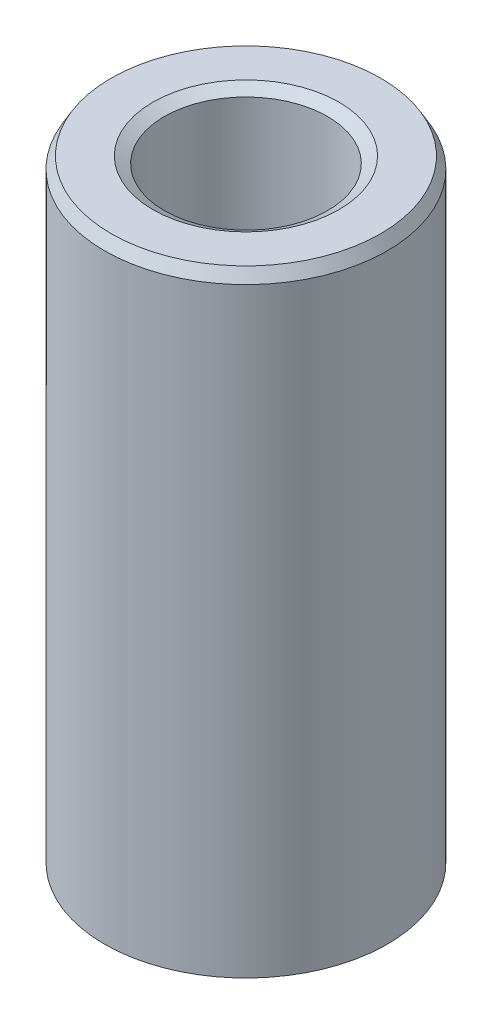
SolidWorks part; units mm, degrees
ref_plane "Front Plane" through (0, 0, 0) normal (0, 0, 1) x (1, 0, 0)
ref_plane "Top Plane" through (0, 0, 0) normal (0, 1, 0) x (1, 0, 0)
ref_plane "Right Plane" through (0, 0, 0) normal (1, 0, 0) x (0, 0, -1)
sketch "Sketch1" plane through (0, 0, 0) normal (0, 1, 0) x (1, 0, 0)
  circle A0 centre (0, 0) radius 45
  dimension "SLEEVE_OD" = 90
extrude "Boss-Extrude1" add sketch "Sketch1" along normal blind 196.9015
sketch "Sketch2" plane through (0, 0, 0) normal (0, 1, 0) x (1, 0, 0)
  circle A0 centre (0, 0) radius 25.97
  dimension "BORE_D" = 51.94
extrude "Cut-Extrude1" cut sketch "Sketch2" along normal through all
chamfer "Chamfer1" distance 3.6605 angle 30 4 edges at (0, 196.9015, 25.97) (0, 0, 25.97) (0, 0, 45) (0, 196.9015, 45) first distance on face at (0, 196.9015, 25.97) first distance on face at (0, 0, 25.97) first distance on face at (0, 196.9015, 45)
